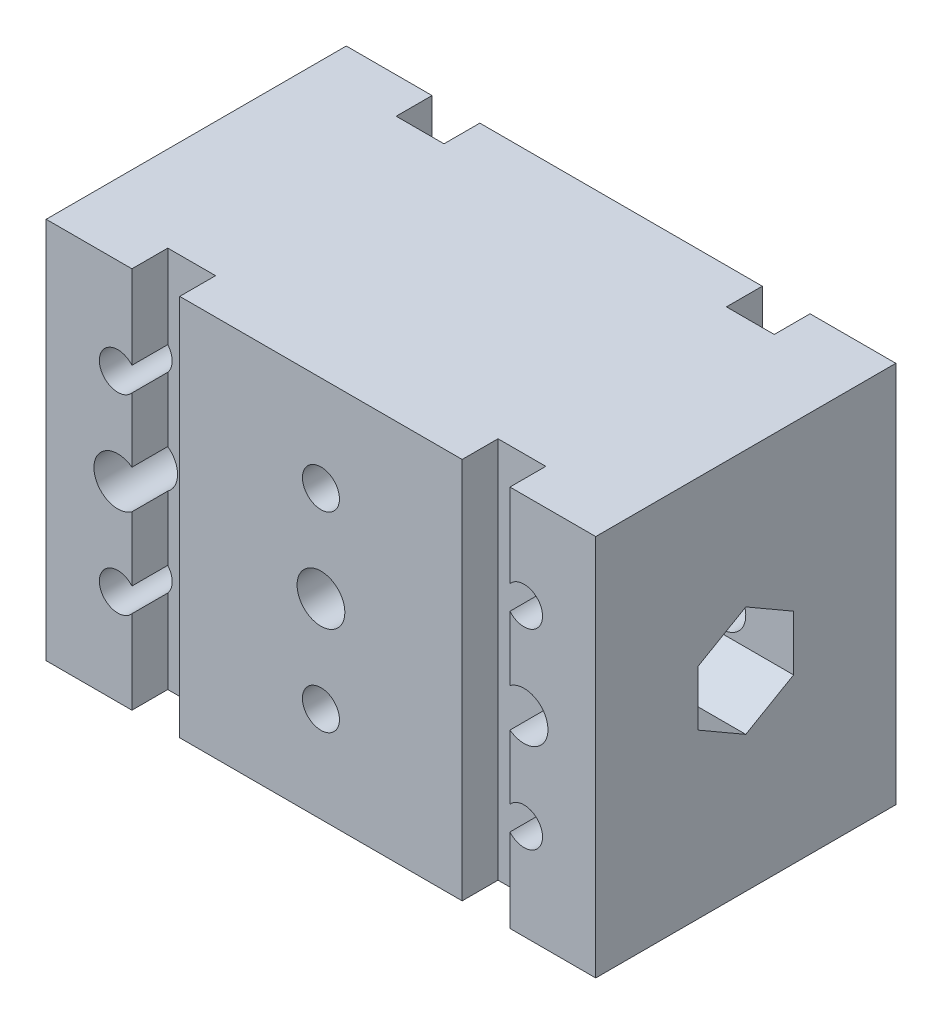
SolidWorks part; units mm, degrees
material "PET"
ref_plane "Front" through (0, 0, 0) normal (0, 0, 1) x (1, 0, 0)
ref_plane "Top" through (0, 0, 0) normal (0, 1, 0) x (1, 0, 0)
ref_plane "Right" through (0, 0, 0) normal (1, 0, 0) x (0, 0, -1)
sketch "Sketch1" plane through (0, 0, 0) normal (1, 0, 0) x (0, 0, -1)
  line L1 (19.939, -25.4) -> (-19.939, -25.4)
  line L2 (19.939, -25.4) -> (19.939, 25.4)
  line L3 (19.939, 25.4) -> (-19.939, 25.4)
  line L4 (-19.939, -25.4) -> (-19.939, 25.4)
  line L5 (19.939, -25.4) -> (-19.939, 25.4) construction
  line L6 (19.939, 25.4) -> (-19.939, -25.4) construction
  point P0 (0, 0)
  dimension "D1" = 50.8
  dimension "D2" = 39.878
extrude "Boss-Extrude1" add sketch "Sketch1" along normal blind 73.025
sketch "Sketch3" plane through (73.025, 0, 0) normal (1, 0, 0) x (0, 0, -1)
  line L1 (6.35, 3.6662) -> (0, 7.3323)
  line L2 (0, 7.3323) -> (-6.35, 3.6662)
  line L3 (-6.35, 3.6662) -> (-6.35, -3.6662)
  line L4 (-6.35, -3.6662) -> (0, -7.3323)
  line L5 (0, -7.3323) -> (6.35, -3.6662)
  line L6 (6.35, -3.6662) -> (6.35, 3.6662)
  circle A0 centre (0, 0) radius 6.35 construction
  dimension "D1" = 12.7
extrude "Cut-Extrude2" cut sketch "Sketch3" against normal through all
ref_axis "Axis1" through (-80.9, 0, 0) along (1, 0, 0)
sketch "Sketch9" plane through (0, 0, 19.939) normal (0, 0, 1) x (1, 0, 0)
  line L0 (9.525, 0) -> (36.5125, 0) construction
  line L1 (36.5125, 0) -> (63.5, 0) construction
  line L2 (0, 25.4) -> (0, -25.4) construction
  line L3 (73.025, 25.4) -> (73.025, -25.4) construction
  circle A0 centre (9.525, 0) radius 3.175
  circle A1 centre (36.5125, 0) radius 3.175
  circle A2 centre (63.5, 0) radius 3.175
  dimension "D1" = 6.35
  dimension "D2" = 9.525
  dimension "D3" = 9.525
extrude "Cut-Extrude4" cut sketch "Sketch9" against normal through all
sketch "Sketch4" plane through (0, 25.4, 0) normal (0, 1, 0) x (1, 0, 0)
  line L0 (73.025, 19.939) -> (0, 19.939) construction
  line L1 (11.397, -19.939) -> (17.747, -19.939)
  line L2 (11.397, -19.939) -> (11.397, -15.1765)
  line L3 (11.397, -15.1765) -> (17.747, -15.1765)
  line L4 (17.747, -19.939) -> (17.747, -15.1765)
  line L5 (11.397, -19.939) -> (17.747, -15.1765) construction
  line L6 (11.397, -15.1765) -> (17.747, -19.939) construction
  line L7 (55.278, -15.1765) -> (61.628, -15.1765)
  line L8 (55.278, -15.1765) -> (55.278, -19.939)
  line L9 (55.278, -19.939) -> (61.628, -19.939)
  line L10 (61.628, -15.1765) -> (61.628, -19.939)
  line L11 (55.278, -15.1765) -> (61.628, -19.939) construction
  line L12 (55.278, -19.939) -> (61.628, -15.1765) construction
  line L13 (55.278, 19.939) -> (61.628, 19.939)
  line L14 (55.278, 19.939) -> (55.278, 15.1765)
  line L15 (55.278, 15.1765) -> (61.628, 15.1765)
  line L16 (61.628, 19.939) -> (61.628, 15.1765)
  line L17 (55.278, 19.939) -> (61.628, 15.1765) construction
  line L18 (55.278, 15.1765) -> (61.628, 19.939) construction
  line L19 (11.397, 19.939) -> (17.747, 19.939)
  line L20 (11.397, 19.939) -> (11.397, 15.1765)
  line L21 (11.397, 15.1765) -> (17.747, 15.1765)
  line L22 (17.747, 19.939) -> (17.747, 15.1765)
  line L23 (11.397, 19.939) -> (17.747, 15.1765) construction
  line L24 (11.397, 15.1765) -> (17.747, 19.939) construction
  line L25 (73.025, 19.939) -> (73.025, -19.939) construction
  line L26 (0, 19.939) -> (0, -19.939) construction
  line L29 (73.025, -19.939) -> (0, -19.939) construction
  point P0 (14.572, -17.5578)
  point P5 (58.453, -17.5578)
  point P10 (58.453, 17.5578)
  point P15 (14.572, 17.5577)
  dimension "D1" = 11.397
  dimension "D2" = 6.35
  dimension "D3" = 4.7625
  dimension "D4" = 11.397
extrude "Cut-Extrude3" cut sketch "Sketch4" against normal through all
sketch "Sketch7" plane through (0, 0, 19.939) normal (0, 0, 1) x (1, 0, 0)
  line L0 (73.025, 25.4) -> (61.628, 25.4) construction
  line L1 (0, 25.4) -> (0, -25.4) construction
  line L2 (73.025, 25.4) -> (73.025, -25.4) construction
  line L3 (9.525, 12.7) -> (36.5125, 12.7) construction
  line L4 (36.5125, 12.7) -> (63.5, 12.7) construction
  point P0 (9.525, 12.7)
  point P2 (36.5125, 12.7)
  point P4 (63.5, 12.7)
  point P6 (63.5, -12.7)
  point P8 (36.5125, -12.7)
  point P10 (9.525, -12.7)
  dimension "D1" = 25.4
  dimension "D2" = 12.7
  dimension "D3" = 9.525
  dimension "D4" = 9.525
hole_wizard "#10 (0.1935) Diameter Hole1" positions "Sketch7" profile "Sketch6" hole size "#10" standard "ANSI Inch" end condition up to next
sketch "Sketch6" plane through (9.525, 12.7, 19.939) normal (1, 0, 0) x (0, -1, 0)
  line L0 (0, 0) -> (0, 39.878)
  line L1 (0, 39.878) -> (2.4574, 39.878)
  line L2 (2.4574, 39.878) -> (2.4574, 0)
  line L5 (2.4574, 0) -> (0, 0)
  line L11 (0, -6.35) -> (0, 107.95) construction
  dimension "Thru Hole Dia." = 4.9149
  dimension "Thru Hole Depth" = 39.878
